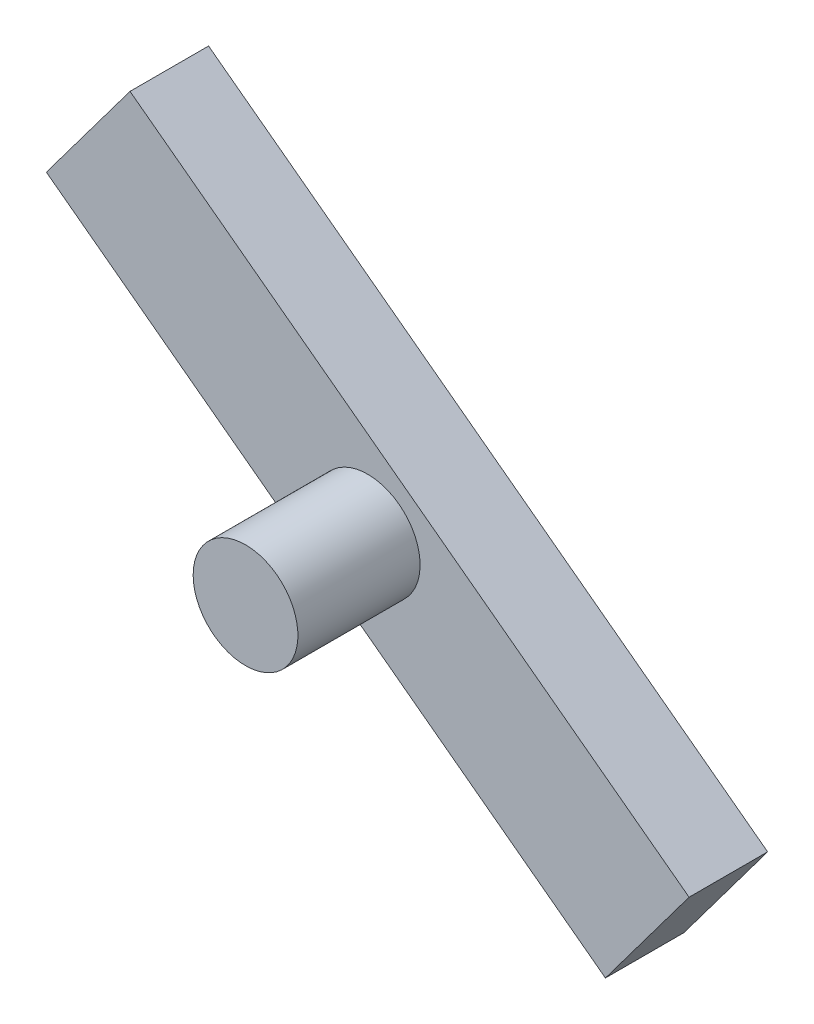
SolidWorks part; units mm, degrees
material "NEOPRENO"
ref_plane "Alzado" through (0, 0, 0) normal (0, 0, 1) x (1, 0, 0)
ref_plane "Planta" through (0, 0, 0) normal (0, 1, 0) x (1, 0, 0)
ref_plane "Vista lateral" through (0, 0, 0) normal (1, 0, 0) x (0, 0, -1)
sketch3d "Sk_Vastago"
  line L0 (-263.1284, 316.5049, 22) -> (-263.1284, 316.5049, 15)
sweep "Vastago" add path "Sk_Vastago" circular profile diameter 6 parameters "D3"=6
sketch "Sk_Goma" plane through (0, 0, 0) normal (0, 0, 1) x (1, 0, 0)
  line L0 (-249.5118, 301.3198) -> (-244.7188, 307.725)
  line L1 (-244.7188, 307.725) -> (-276.7449, 331.6901)
  line L2 (-276.7449, 331.6901) -> (-281.538, 325.2848)
  line L3 (-281.538, 325.2848) -> (-249.5118, 301.3198)
extrude "Goma" add sketch "Sk_Goma" along normal blind 4.5 from offset 10.5
